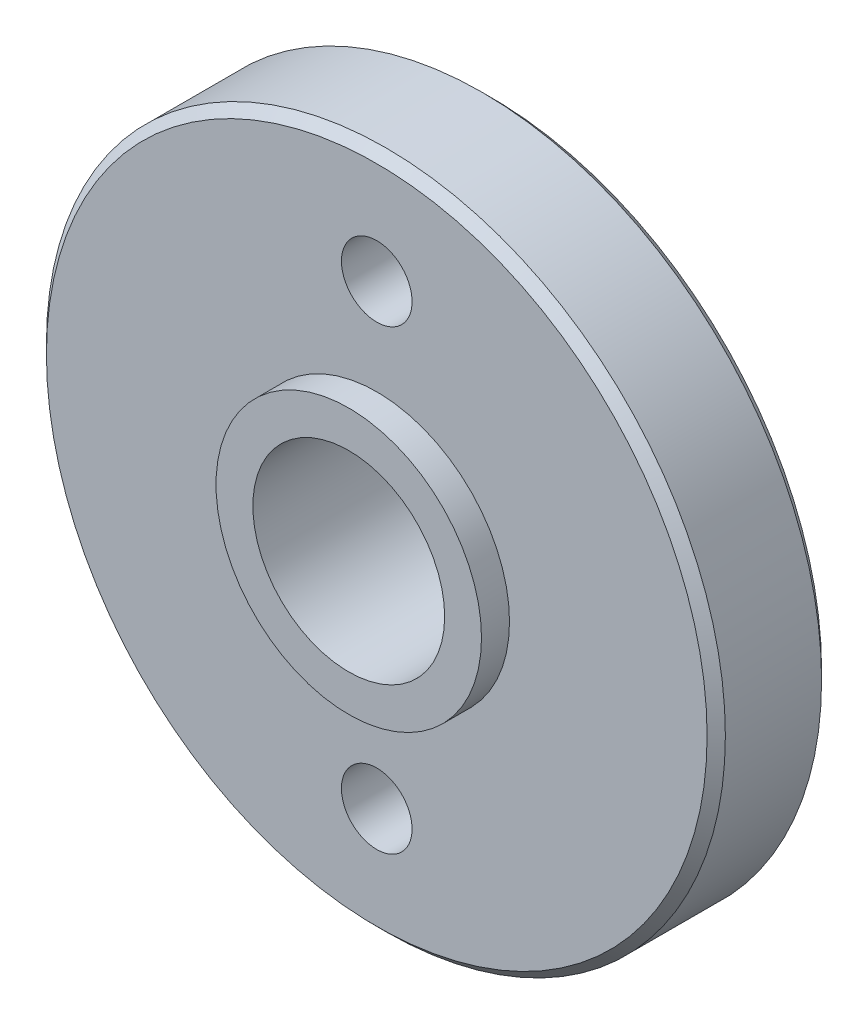
SolidWorks part; units mm, degrees
material "ASTM A36 Steel"
ref_plane "Front Plane" through (0, 0, 0) normal (0, 0, 1) x (1, 0, 0)
ref_plane "Top Plane" through (0, 0, 0) normal (0, 1, 0) x (1, 0, 0)
ref_plane "Right Plane" through (0, 0, 0) normal (1, 0, 0) x (0, 0, -1)
sketch "Sketch1" plane through (0, 0, 0) normal (1, 0, 0) x (0, 0, -1)
  line L0 (14.8005, 0) -> (19.0582, 0) construction
  line L1 (0, 14.1605) -> (4.7752, 14.1605)
  line L2 (0, 14.1605) -> (0, 5.5372)
  line L3 (-1.1684, 4.0005) -> (8.3566, 4.0005)
  line L4 (11.684, 5.5626) -> (11.684, 0)
  line L5 (0, 5.5372) -> (-1.1684, 5.5372)
  line L6 (-1.1684, 5.5372) -> (-1.1684, 4.0005)
  line L8 (8.3566, 4.0005) -> (10.7603, 0)
  line L9 (10.7603, 0) -> (11.684, 0)
  line L10 (11.684, 5.5626) -> (4.7752, 5.5626)
  line L11 (4.7752, 5.5626) -> (4.7752, 14.1605)
  dimension "D1" = 11.684
  dimension "D2" = 8.001
  dimension "D3" = 28.321
  dimension "D4" = 11.1252
  dimension "D5" = 4.7752
  dimension "D6" = 11.0744
  dimension "D7" = 59
  dimension "D8" = 9.525
  dimension "D9" = 1.1684
revolve "Revolve1" add sketch "Sketch1" angle 360 about L0
ref_axis "Axis1" through (0, 0, 1.811) along (0, 0, -1)
chamfer "Chamfer1" distance 0.381 angle 45 2 edges at (14.1605, 0, 0) (14.1605, 0, -4.7752)
hole_wizard "#32 (0.116) Diameter Hole1" positions "Sketch3" profile "Sketch2" hole size "#32" standard "ANSI Inch" end condition up to next
sketch "Sketch3" plane through (0, 0, -4.7752) normal (0, 0, -1) x (-1, 0, 0)
  point P0 (0, 9.525)
  point P2 (0, -9.525)
  dimension "D1" = 9.525
  dimension "D2" = 9.525
sketch "Sketch2" plane through (0, 9.525, -4.7752) normal (1, 0, 0) x (0, 1, 0)
  line L0 (0, 0) -> (0, 4.7752)
  line L1 (0, 4.7752) -> (1.4732, 4.7752)
  line L2 (1.4732, 4.7752) -> (1.4732, 0)
  line L5 (1.4732, 0) -> (0, 0)
  line L11 (0, -6.35) -> (0, 107.95) construction
  dimension "Thru Hole Dia." = 2.9464
  dimension "Thru Hole Depth" = 4.7752
chamfer "Chamfer2" distance 2.032 angle 45 1 edges at (5.5626, 0, -11.684)
sketch "Sketch4" plane through (0, 0, 1.1684) normal (0, 0, 1) x (1, 0, 0)
  line L0 (0, -15.4033) -> (0, 15.1707) construction
pattern_linear "LPattern1" [suppressed] count 2 spacing 101.6 along (0, 1, 0) of bodies 104
sketch "Sketch5" [suppressed] plane through (0, 0, 1.1684) normal (0, 0, 1) x (1, 0, 0)
  circle A0 centre (0, 101.6) radius 14.1605
  circle A1 centre (0, 0) radius 14.1605
  circle A2 centre (0, 0) radius 14.1605 construction
  circle A3 centre (0, 101.6) radius 14.1605 construction
